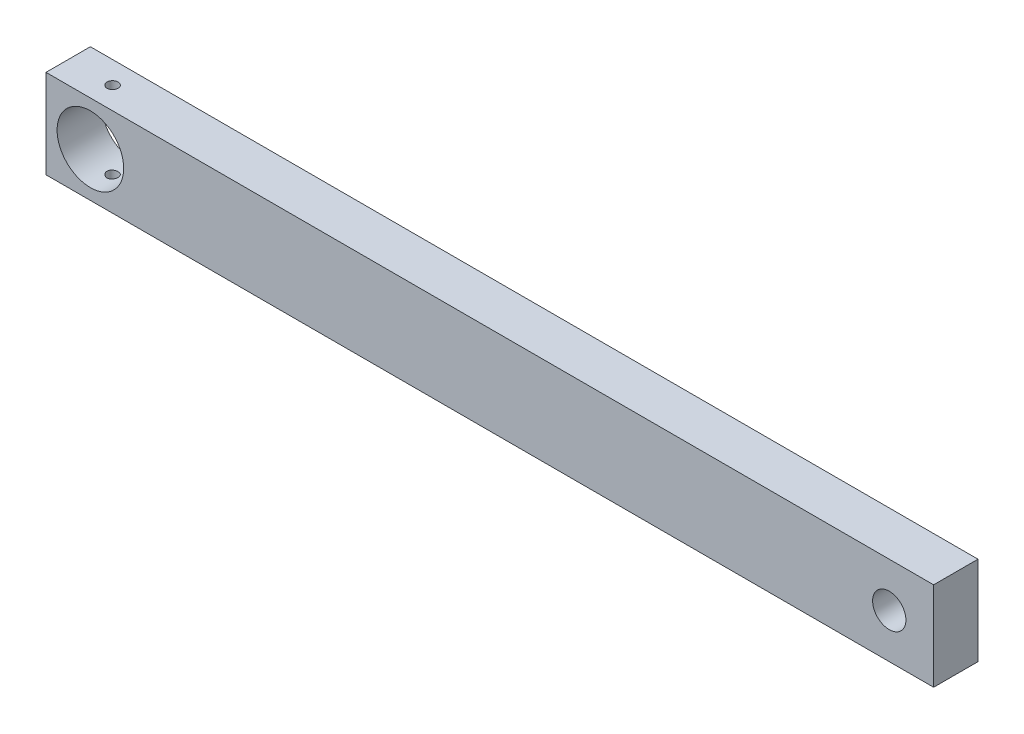
SolidWorks part; units mm, degrees
ref_plane "Front Plane" through (0, 0, 0) normal (0, 0, 1) x (1, 0, 0)
ref_plane "Top Plane" through (0, 0, 0) normal (0, 1, 0) x (1, 0, 0)
ref_plane "Right Plane" through (0, 0, 0) normal (1, 0, 0) x (0, 0, -1)
sketch "Sketch1" plane through (0, 0, 0) normal (0, 0, 1) x (1, 0, 0)
  line L1 (0, 0) -> (127, 0)
  line L2 (0, 0) -> (0, 12.7)
  line L3 (0, 12.7) -> (127, 12.7)
  line L4 (127, 0) -> (127, 12.7)
  circle A2 centre (6.35, 6.35) radius 4.7625
  circle A3 centre (120.65, 6.35) radius 2.3813
  dimension "D9" = 4.7625
  dimension "D10" = 6.35
  dimension "D11" = 6.35
  dimension "D12" = 9.525
  dimension "D13" = 6.35
  dimension "D14" = 6.35
  dimension "D1" = 12.7
  dimension "D2" = 127
other "AlignGroup1"
extrude "Boss-Extrude1" add sketch "Sketch1" along normal blind 6.35
sketch "Sketch2" plane through (0, 12.7, 0) normal (0, 1, 0) x (1, 0, 0)
  line L0 (0, -6.35) -> (0, 0) construction
  line L1 (127, -6.35) -> (0, -6.35) construction
  circle A0 centre (6.35, -3.175) radius 0.7874
  dimension "D1" = 1.5748
  dimension "D2" = 6.35
  dimension "D3" = 3.175
extrude "Cut-Extrude1" cut sketch "Sketch2" against normal blind 12.7
